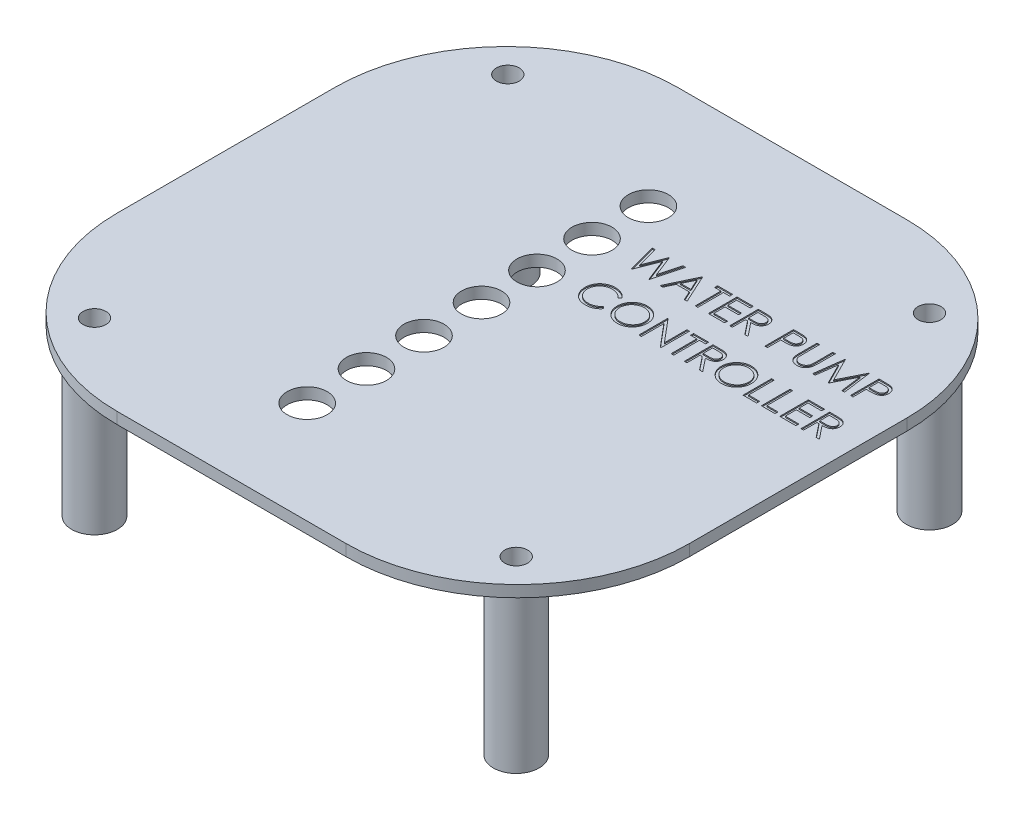
SolidWorks part; units mm, degrees
ref_plane "Front Plane" through (0, 0, 0) normal (0, 0, 1) x (1, 0, 0)
ref_plane "Top Plane" through (0, 0, 0) normal (0, 1, 0) x (1, 0, 0)
ref_plane "Right Plane" through (0, 0, 0) normal (1, 0, 0) x (0, 0, -1)
sketch "Sketch8" plane through (0, 0, 0) normal (1, 0, 0) x (0, 0, -1)
  line L0 (111.1859, 204.2632) -> (793.8526, 204.2632) construction
sketch "Sketch4" plane through (0, 0, 0) normal (0, 1, 0) x (1, 0, 0)
  line L0 (102.2144, 571.953) -> (742.2144, 571.953) construction
sketch "Sketch1" plane through (0, 0, 0) normal (0, 1, 0) x (1, 0, 0)
  line L0 (163.1224, 741.5892) -> (896.4526, 741.5892) construction
  line L2 (-20, -49) -> (20, -49)
  line L3 (-50, -19) -> (-50, 19)
  line L4 (-20, 49) -> (20, 49)
  line L5 (50, -19) -> (50, 19)
  line L6 (-50, -49) -> (50, 49) construction
  line L7 (-50, 49) -> (50, -49) construction
  line L8 (-18, -47) -> (18, -47)
  line L9 (-48, -17) -> (-48, 17)
  line L10 (-18, 47) -> (18, 47)
  line L11 (48, -17) -> (48, 17)
  line L12 (-48, -47) -> (48, 47) construction
  line L13 (-48, 47) -> (48, -47) construction
  line L21 (0, 0) -> (0, 63.1182)
  arc A0 (-48, 17) -> (-18, 47) centre (-18, 17) cw
  arc A1 (-18, -47) -> (-48, -17) centre (-18, -17) cw
  arc A2 (18, -47) -> (48, -17) centre (18, -17) ccw
  arc A3 (48, 17) -> (18, 47) centre (18, 17) ccw
  arc A4 (-50, -19) -> (-20, -49) centre (-20, -19) ccw
  arc A5 (20, -49) -> (50, -19) centre (20, -19) ccw
  arc A6 (50, 19) -> (20, 49) centre (20, 19) ccw
  arc A7 (-50, 19) -> (-20, 49) centre (-20, 19) cw
  circle A8 centre (-36.8433, 36.1065) radius 2
  circle A9 centre (-36.8433, 36.1065) radius 1.2
  circle A10 centre (36.1065, 36.8433) radius 1.2
  circle A11 centre (36.1065, 36.8433) radius 2
  circle A12 centre (36.8433, -36.1065) radius 1.2
  circle A13 centre (36.8433, -36.1065) radius 2
  circle A14 centre (-36.1065, -36.8433) radius 1.2
  circle A15 centre (-36.1065, -36.8433) radius 2
  arc A18 (-7.9908, 48.9778) -> (-7.9689, 49) centre (-14.2443, 55.1548) ccw
  circle A22 centre (-36.8433, 36.1065) radius 4
  circle A23 centre (36.1065, 36.8433) radius 4
  circle A24 centre (-36.1065, -36.8433) radius 4
  circle A25 centre (36.8433, -36.1065) radius 4
  point P2 (0, 0)
  point P8 (0, 0)
  dimension "D5" = 30
  dimension "D6" = 30
  dimension "D7" = 30
  dimension "D8" = 2.4
  dimension "D9" = 4
  dimension "D10" = 4
  dimension "D11" = 8
  dimension "D12" = 8
  dimension "D13" = 8
  dimension "D14" = 8
  dimension "D1" = 98
  dimension "D2" = 100
  dimension "D3" = 96
  dimension "D4" = 94
extrude "Boss-Extrude1" add sketch "Sketch1" along normal blind 2 contours A7 L3 A4 L2 A5 L5 A6 L4 L10 A3 L11 A2 L8 A1 L9 A0 | L11 A3 L10 A0 L9 A1 L8 A2 A15 A13 A11 A8 region at (9, 0, -45.6564) region at (-40.2232, 0, 39.2232)
sketch "Sketch5" plane through (0, 0, 0) normal (0, 1, 0) x (1, 0, 0)
  circle A0 centre (-4.6392, 28.4786) radius 3.5
  circle A1 centre (-4.6392, 18.6219) radius 3.5
  circle A2 centre (-4.6392, 9.0043) radius 3.5
  circle A3 centre (-4.6392, -0.688) radius 3.5
  circle A4 centre (-4.6392, -10.7375) radius 3.5
  circle A5 centre (-4.6392, -20.7897) radius 3.5
  circle A6 centre (-4.6392, -31.1468) radius 3.5
  dimension "D1" = 7
  dimension "D2" = 7
  dimension "D3" = 7
  dimension "D4" = 7
  dimension "D5" = 7
  dimension "D6" = 7
extrude "Cut-Extrude1" cut sketch "Sketch5" along normal blind 10
sketch "Sketch7" plane through (0, 2, 0) normal (0, 1, 0) x (1, 0, 0)
  text T0 "WATER PUMP\r\nCONTROLLER" font "Century Gothic" height 5
extrude "Cut-Extrude2" cut sketch "Sketch7" against normal blind 0.2
extrude "Boss-Extrude2" add sketch "Sketch1<6>" along normal blind 2 and the other way blind 28 contours A10 | A22 | A9 | A24 | A14 | A25 | A12 | A23
sketch "Sketch1<6>" plane through (0, 0, 0) normal (0, 1, 0) x (1, 0, 0) same geometry as "Sketch1"
extrude "Cut-Extrude3" cut sketch "Sketch1<7>" against normal blind 26 and the other way blind 3 contours A13 | A11 | A8 | A15
sketch "Sketch1<7>" plane through (0, 0, 0) normal (0, 1, 0) x (1, 0, 0) same geometry as "Sketch1"
